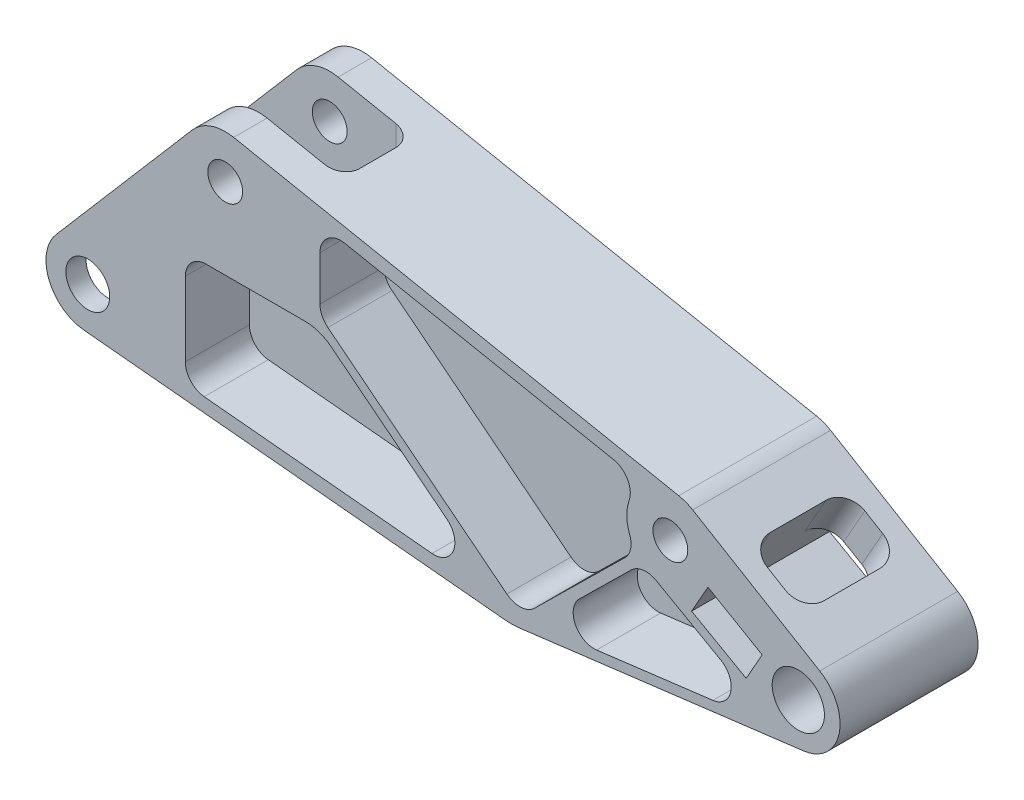
SolidWorks part; units mm, degrees
material "6061-T6 (SS)"
ref_plane "Front Plane" through (0, 0, 0) normal (1, 0, 0) x (0, 1, 0)
ref_plane "Top Plane" through (0, 0, 0) normal (0, 0, 1) x (0, 1, 0)
ref_plane "Right Plane" through (0, 0, 0) normal (0, 1, 0) x (-1, 0, 0)
sketch "Sketch1" plane through (0, 0, 0) normal (0, 0, 1) x (0, 1, 0)
  line L1 (21.356, 21.793) -> (37.358, 102.9455)
  line L2 (5.8317, 135.319) -> (34.7405, 110.5039)
  line L3 (6.5414, -3.9083) -> (20.3824, 19.2574)
  line L5 (14.8385, 114.2971) -> (14.8385, 127.5877)
  line L6 (16.8705, 89.241) -> (16.8705, 125.8434)
  line L9 (-2.4791, 111.7571) -> (11.0285, 111.7571)
  line L10 (16.8705, 89.241) -> (34.6557, 89.241)
  line L12 (4.2983, 19.4547) -> (-1.3308, 9.5091)
  line L14 (14.8385, 107.9471) -> (14.8385, 89.9006)
  line L15 (-13.1015, 50.4298) -> (20.0455, 92.416) construction
  line L16 (-6.2716, 108.311) -> (-10.2563, 66.785)
  line L17 (-14.2126, 52.1469) -> (-6.7167, 130.2649)
  line L20 (13.1993, 85.1789) -> (-3.4733, 64.0603)
  line L21 (15.9233, 85.7599) -> (-9.8354, 53.1323)
  line L23 (30.7695, 82.662) -> (21.1158, 33.7042)
  line L25 (18.9137, 87.209) -> (27.0315, 87.209)
  line L26 (4.2983, 19.4547) -> (16.4059, 12.6019)
  line L27 (-1.3308, 9.5091) -> (10.5427, 2.7888)
  line L28 (-13.1015, 50.4298) -> (13.5685, 23.3286) construction
  line L29 (-10.4937, 36.7653) -> (-7.8375, 15.5634)
  line L30 (-9.5606, 48.0991) -> (6.6502, 31.6262)
  line L31 (-0.7413, 14.1604) -> (5.9072, 25.9071)
  line L32 (14.8385, 114.2971) -> (-8.2489, 114.2971)
  line L33 (5.3071, 30.4561) -> (-3.9976, 39.9113)
  line L34 (-7.5609, -0.9472) -> (-14.2126, 52.1469)
  line L35 (0, 0) -> (13.5685, 23.3286)
  circle A0 centre (0, 0) radius 4.7625
  circle A1 centre (29.5705, 104.481) radius 3.175
  circle A2 centre (0.8685, 129.5371) radius 4
  circle A3 centre (13.5685, 23.3286) radius 3.175
  arc A4 (-7.5609, -0.9472) -> (6.5414, -3.9083) centre (0, 0) ccw
  arc A5 (-6.7167, 130.2649) -> (5.8317, 135.319) centre (0.8685, 129.5371) cw
  arc A6 (37.358, 102.9455) -> (34.7405, 110.5039) centre (29.5705, 104.481) ccw
  arc A7 (20.3824, 19.2574) -> (21.356, 21.793) centre (13.5685, 23.3286) ccw
  arc A17 (21.1158, 33.7042) -> (16.1423, 30.8372) centre (17.3778, 34.4413) cw
  arc A23 (14.8385, 89.9006) -> (13.1993, 85.1789) centre (7.2185, 89.9006) cw
  arc A24 (-10.2563, 66.785) -> (-3.4733, 64.0603) centre (-6.4637, 66.4211) ccw
  arc A25 (27.0315, 87.209) -> (30.7695, 82.662) centre (27.0315, 83.399) cw
  arc A26 (18.9137, 87.209) -> (15.9233, 85.7599) centre (18.9137, 83.399) ccw
  arc A28 (-2.4791, 111.7571) -> (-6.2716, 108.311) centre (-2.4791, 107.9471) ccw
  arc A29 (-9.8354, 53.1323) -> (-9.5606, 48.0991) centre (-6.845, 50.7714) ccw
  arc A30 (-10.4937, 36.7653) -> (-3.9976, 39.9113) centre (-6.7132, 37.2389) cw
  arc A32 (6.6502, 31.6262) -> (10.7288, 30.7407) centre (9.3658, 34.2986) ccw
  arc A33 (-7.8375, 15.5634) -> (-0.7413, 14.1604) centre (-4.057, 16.037) ccw
  arc A34 (11.0285, 111.7571) -> (14.8385, 107.9471) centre (11.0285, 107.9471) cw
  circle A35 centre (20.0455, 92.416) radius 3.175 construction
  arc A36 (10.7288, 30.7407) -> (16.1423, 30.8372) centre (13.5685, 23.3286) cw
  arc A37 (5.3071, 30.4561) -> (5.9072, 25.9071) centre (2.5915, 27.7837) cw
  dimension "D1" = 38.1
  dimension "D4" = 6.35
  dimension "D5" = 9.525
  dimension "D6" = 8
  dimension "D7" = 26.9875
  dimension "D8" = 7.62
  dimension "D9" = 7.62
  dimension "D10" = 7.9375
  dimension "D11" = 7.9375
  dimension "D19" = 2.54
  dimension "D22" = 1.778
  dimension "D24" = 3.81
  dimension "D25" = 3.81
  dimension "D26" = 1.778
  dimension "D29" = 3.81
  dimension "D30" = 12.7
  dimension "D31" = 3.81
  dimension "D32" = 3.81
  dimension "D33" = 7.62
  dimension "D34" = 3.81
  dimension "D35" = 3.81
  dimension "D36" = 1.27
  dimension "D14" = 3.81
  dimension "D20" = 3.81
  dimension "D28" = 3.81
  dimension "D39" = 6.35
  dimension "D40" = 1.778
  dimension "D12" = 3.81
  dimension "D2" = 129.54
  dimension "D3" = 108.585
  dimension "D13" = 15.24
  dimension "D15" = 13.97
  dimension "D16" = 12.7
  dimension "D17" = 2.032
  dimension "D18" = 2.032
  dimension "D21" = 1.778
  dimension "D23" = 2.54
  dimension "D27" = 2.54
  dimension "D37" = 0.889
  dimension "D38" = 15.24
  dimension "D41" = 13.97
extrude "Boss-Extrude1" add sketch "Sketch1" along normal mid plane 25.146 contours L1 A6 L2 L6 L10 A1 | L3 A7 L1 L10 L6 L2 L5 A4 L27 L12 L26 A28 A23 L20 A24 L16 A17 A3 A0 L23 L21 A26 L25 A25 | A5 L5 L2 A2 | L12 L27 L3 L26 region at (-20.9986, 19.6363, 0) region at (-103.8939, 25.4238, 0) region at (-9.6254, 10.0977, 0) region at (-123.5763, 3.4351, 0)
extrude "Boss-Extrude2" add sketch "Sketch1<5>" along normal mid plane 1.778 contours L16 A24 L20 A23 | A17 | L23 A25 L25 A26 L21 | L29 A33 L31 L33 A30 region at (-90.503, 1.8814, 0) region at (-57.96, 12.4468, 0) region at (-26.9438, -3.1281, 0)
sketch "Sketch1<5>" plane through (0, 0, 0) normal (0, 0, 1) x (0, 1, 0) same geometry as "Sketch1"
extrude "Cut-Extrude1" cut sketch "Sketch1<6>" against normal mid plane 12.954 contours L1 A6 L2 L6 L10 A1 region at (-103.8939, 25.4238, 0)
sketch "Sketch1<6>" plane through (0, 0, 0) normal (0, 0, 1) x (0, 1, 0) same geometry as "Sketch1"
extrude "Cut-Extrude2" cut sketch "Sketch1<7>" against normal mid plane 17.78 contours A5 L5 L2 A2 region at (-123.5763, 3.4351, 0)
sketch "Sketch1<7>" plane through (0, 0, 0) normal (0, 0, 1) x (0, 1, 0) same geometry as "Sketch1"
extrude "Cut-Extrude3" cut sketch "Sketch1<9>" against normal mid plane 17.78 contours L12 L27 L3 L26 region at (-9.6254, 10.0977, 0)
sketch "Sketch1<9>" plane through (0, 0, 0) normal (0, 0, 1) x (0, 1, 0) same geometry as "Sketch1"
fillet "Fillet1" radius 3.81 8 edges at (-120.9424, 14.8385, 8.89) (-120.9424, 14.8385, -8.89) (-107.5422, 16.8705, 6.477) (-107.5422, 16.8705, -6.477) (-4.6881, 7.1871, -8.89) (-14.5343, 12.9917, -8.89) (-14.5343, 12.9917, 8.89) (-4.6881, 7.1871, 8.89)
fillet "Fillet2" radius 3.175 10 edges at (-89.241, 27.6681, -6.477) (-89.241, 17.9864, -5.3611) (-89.241, 27.6681, 6.477) (-89.241, 17.9864, 5.3611) (-89.241, 16.8705, 0) (-114.2971, 1.3898, -8.89) (-114.2971, 13.7226, -7.7741) (-114.2971, 1.3898, 8.89) (-114.2971, 13.7226, 7.7741) (-114.2971, 14.8385, 0)
sketch "Sketch2" plane through (0, 0, 0) normal (0, 0, 1) x (0, 1, 0)
  line L0 (0.8685, 129.5371) -> (-82.2041, 143.266)
  line L1 (29.5705, 104.481) -> (77.0079, 96.6413)
  line L2 (0.8685, 129.5371) -> (0, 0) construction
  dimension "D1" = 99
fillet "Fillet3" radius 12.7 1 edges at (-52.1469, -14.2126, 0)
